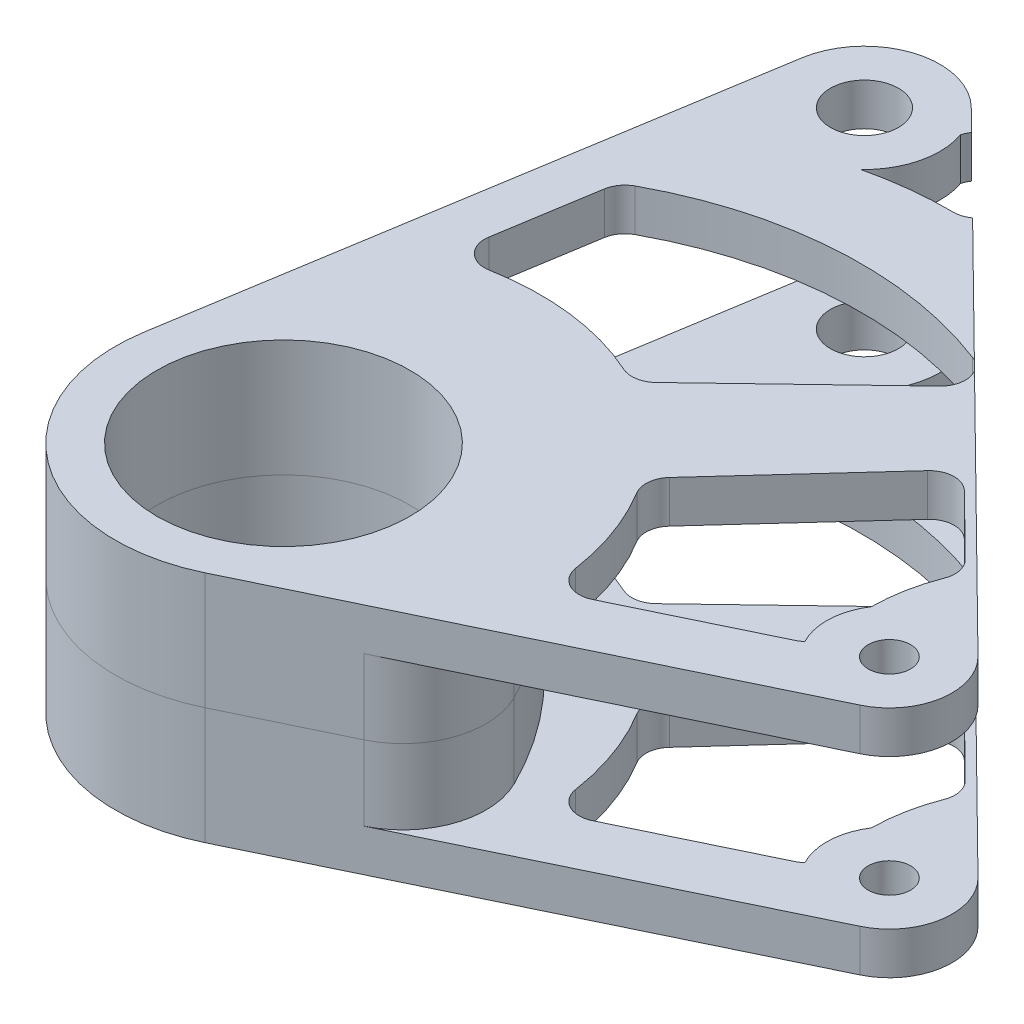
SolidWorks part; units mm, degrees
note: '?' marks a value the reader was unsure of.
ref_plane "Front Plane" through (0, 0, 0) normal (0, 0, 1) x (1, 0, 0)
ref_plane "Top Plane" through (0, 0, 0) normal (0, 1, 0) x (1, 0, 0)
ref_plane "Right Plane" through (0, 0, 0) normal (1, 0, 0) x (0, 0, -1)
sketch "Sketch1" plane through (0, 0, 0) normal (0, 1, 0) x (1, 0, 0)
  line L0 (0, 70) -> (0, 0) construction
  line L1 (-8.9838, 71.4495) -> (-19.9915, 3.2255)
  line L2 (6.3888, 76.4802) -> (64.0847, 19.5984)
  line L3 (8.7886, -18.2434) -> (62.0608, 7.4201)
  circle A0 centre (0, 0) radius 15.25
  circle A1 centre (0, 70) radius 4.1
  circle A2 centre (58.7841, 14.222) radius 2.55
  circle A3 centre (0, 70) radius 9.1
  circle A4 centre (0, 0) radius 20.25
  circle A5 centre (58.7841, 14.222) radius 7.55
  point P19 (62.6534, 4.569)
  point P20 (60.48, 13.2348)
  point P21 (0, 0)
  dimension "D1" = 8.2
  dimension "D2" = 30.5
  dimension "D3" = 5.1
  dimension "D5" = 60.48
  dimension "D4" = 70
  dimension "D6" = 5
extrude "Boss-Extrude1" add sketch "Sketch1" along normal blind 5.08
sketch "Sketch3" plane through (0, 5.08, 0) normal (0, 1, 0) x (1, 0, 0)
  line L0 (-5.0948, 58.9775) -> (-4.1917, 64.5744)
  line L1 (13.5985, 74.3126) -> (18.3697, 69.6086)
  line L2 (-7.2099, 45.8684) -> (-9.1421, 33.8926)
  line L3 (-8.9838, 71.4495) -> (-19.9915, 3.2255)
  line L4 (8.7886, -18.2434) -> (62.0608, 7.4201)
  line L5 (64.0847, 19.5984) -> (6.3888, 76.4802)
  line L6 (-8.9838, 71.4495) -> (-19.9915, 3.2255)
  line L7 (8.7886, -18.2434) -> (62.0608, 7.4201)
  line L8 (64.0847, 19.5984) -> (6.3888, 76.4802)
  line L9 (33.5731, 45.4958) -> (16.0989, 28.784)
  line L10 (51.3797, 10.2479) -> (34.9111, 2.3143)
  line L11 (53.1944, 28.9518) -> (45.9826, 36.0618)
  line L12 (41.6602, 35.9474) -> (26.8177, 19.6792)
  circle A0 centre (0, 70) radius 9.1
  circle A1 centre (0, 0) radius 20.25
  circle A2 centre (58.7841, 14.222) radius 7.55
  arc A3 (-1.586, 61.4493) -> (8.5447, 71.6181) centre (0, 70) ccw
  arc A4 (30.642, 4.5741) -> (26.4707, 16.0983) centre (0, 0) ccw
  arc A6 (-19.9915, 3.2255) -> (8.7886, -18.2434) centre (0, 0) ccw
  arc A7 (62.0608, 7.4201) -> (64.0847, 19.5984) centre (58.7841, 14.222) ccw
  arc A8 (6.3888, 76.4802) -> (-8.9838, 71.4495) centre (0, 70) ccw
  arc A9 (-19.9915, 3.2255) -> (8.7886, -18.2434) centre (0, 0) ccw
  arc A10 (62.0608, 7.4201) -> (64.0847, 19.5984) centre (58.7841, 14.222) ccw
  arc A11 (6.3888, 76.4802) -> (-8.9838, 71.4495) centre (0, 70) ccw
  arc A12 (-0.0929, 61.3204) -> (16.241, 64.4724) centre (15.9233, 22.2209) cw
  arc A13 (-5.6773, 48.0282) -> (32.5832, 50.4613) centre (16.0845, 7.8635) cw
  arc A14 (53.001, 13.6247) -> (53.8828, 25.7247) centre (73.0436, 18.2461) cw
  arc A15 (12.7872, 28.2195) -> (-5.6348, 30.4648) centre (0, 0) ccw
  arc A16 (53.1944, 28.9518) -> (53.8828, 25.7247) centre (51.0882, 26.8154) cw
  arc A17 (51.3797, 10.2479) -> (53.001, 13.6247) centre (50.0777, 12.9507) ccw
  arc A18 (34.9111, 2.3143) -> (30.642, 4.5741) centre (33.6091, 5.017) cw
  arc A19 (26.8177, 19.6792) -> (26.4707, 16.0983) centre (29.0339, 17.6572) ccw
  arc A20 (45.9826, 36.0618) -> (41.6602, 35.9474) centre (43.8764, 33.9254) ccw
  arc A21 (32.5832, 50.4613) -> (33.5731, 45.4958) centre (31.4996, 47.6638) cw
  arc A22 (16.0989, 28.784) -> (12.7872, 28.2195) centre (14.0254, 30.9521) cw
  arc A23 (-9.1421, 33.8926) -> (-5.6348, 30.4648) centre (-6.1804, 33.4147) ccw
  arc A24 (-7.2099, 45.8684) -> (-5.6773, 48.0282) centre (-4.2482, 45.3905) cw
  arc A25 (18.3697, 69.6086) -> (16.241, 64.4724) centre (16.2636, 67.4723) cw
  arc A26 (13.5985, 74.3126) -> (8.5447, 71.6181) centre (11.4923, 72.1763) ccw
  arc A27 (-4.1917, 64.5744) -> (-0.0929, 61.3204) centre (-1.23, 64.0965) ccw
  arc A28 (-5.0948, 58.9775) -> (-1.586, 61.4493) centre (-2.1331, 58.4996) cw
  point P49 (14.5834, 27.3346)
  dimension "D1" = 0
  dimension "D2" = 3
extrude "Cut-Extrude1" cut sketch "Sketch3" against normal through all
sketch "Sketch2" plane through (0, 5.08, 0) normal (0, 1, 0) x (1, 0, 0)
  line L0 (8.7886, -18.2434) -> (62.0608, 7.4201) construction
  line L1 (-8.9838, 71.4495) -> (-19.9915, 3.2255) construction
  line L2 (8.7886, -18.2434) -> (21.7397, -12.0043)
  line L3 (-17.4698, 18.8546) -> (-19.9915, 3.2255)
  arc A0 (-19.9915, 3.2255) -> (8.7886, -18.2434) centre (0, 0) ccw construction
  circle A1 centre (0, 0) radius 15.25 construction
  arc A2 (-19.9915, 3.2255) -> (8.7886, -18.2434) centre (0, 0) ccw
  circle A3 centre (0, 0) radius 15.25
  arc A4 (-5.1228, 26.9507) -> (26.3655, 1.4334) centre (-17.1273, -20.0497) cw
  arc A5 (26.3655, 1.4334) -> (21.7397, -12.0043) centre (17.3996, -2.9952) cw
  arc A6 (-5.1228, 26.9507) -> (-17.4698, 18.8546) centre (-7.5974, 17.2618) ccw
  point P15 (29.8824, -8.0816)
  point P18 (-15.9225, 28.4446)
  dimension "D1" = 10
extrude "Boss-Extrude2" add sketch "Sketch2" along normal blind 9
mirror "Mirror1" about plane through (0, 14.08, 0) normal (0, 1, 0) of bodies 102
ref_plane "Plane1" through (0, 14.08, 0) normal (0, -1, 0) x (-1, 0, 0)
ref_axis "Axis1" through (58.7841, 5.08, -14.222) along (0, -1, 0)?
ref_point "Pushrod Pt"
